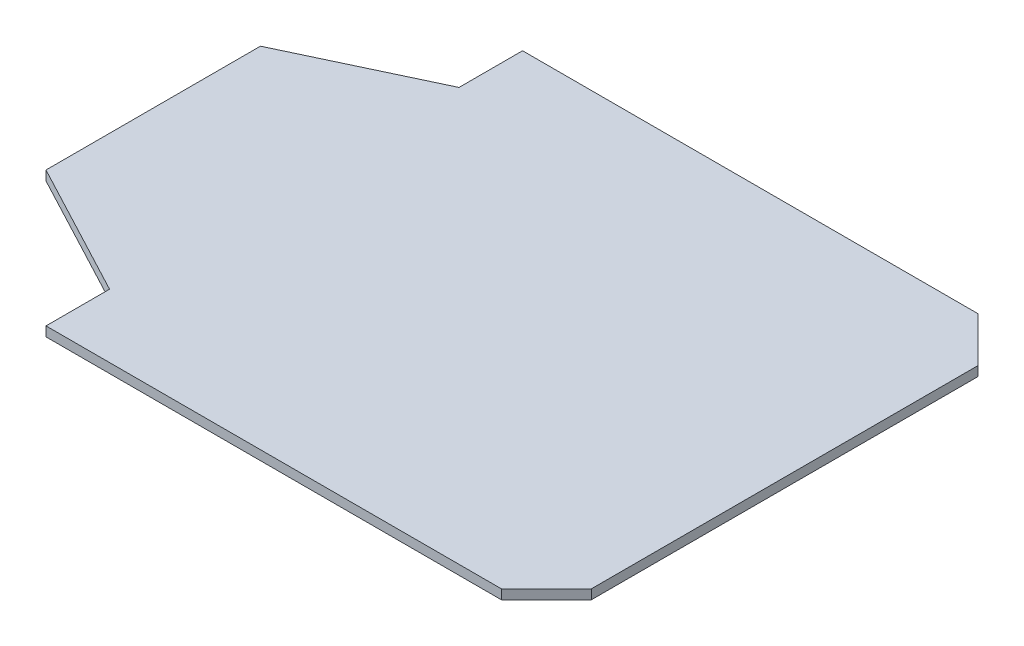
SolidWorks part; units mm, degrees
material "Acrylic (Medium-high impact)"
ref_plane "Front Plane" through (0, 0, 0) normal (0, 0, 1) x (1, 0, 0)
ref_plane "Top Plane" through (0, 0, 0) normal (0, 1, 0) x (1, 0, 0)
ref_plane "Right Plane" through (0, 0, 0) normal (1, 0, 0) x (0, 0, -1)
sketch "Sketch1" plane through (0, 0, 0) normal (0, 1, 0) x (1, 0, 0)
  line L0 (-245.1836, 942.3231) -> (-245.1836, 742.3231)
  line L2 (-145.1836, 692.3231) -> (126.5321, 692.3231)
  line L3 (126.5321, 692.3231) -> (154.8164, 720.6074)
  line L4 (154.8164, 720.6074) -> (154.8164, 964.0388)
  line L6 (126.5321, 992.3231) -> (-145.1836, 992.3231)
  line L8 (126.5321, 992.3231) -> (154.8164, 964.0388)
  line L9 (-145.1836, 692.3231) -> (-245.1836, 692.3231)
  line L10 (-245.1836, 692.3231) -> (-245.1836, 742.3231)
  line L11 (-145.1836, 992.3231) -> (-245.1836, 992.3231)
  line L12 (-245.1836, 992.3231) -> (-245.1836, 942.3231)
  point P2 (154.8164, 842.3231)
  point P9 (-245.1836, 842.3231)
  dimension "D1" = 300
  dimension "D2" = 400
  dimension "D3" = 200
  dimension "D4" = 150
  dimension "D5" = 100
  dimension "D6" = 45
  dimension "D7" = 150
  dimension "D8" = 0
  dimension "D9" = 45
  dimension "D10" = 40
extrude "Boss-Extrude1" add sketch "Sketch1" along normal blind 6 contours L6 L11 L12 L0 L10 L9 L2 L3 L4 L8
sketch "Sketch2" plane through (0, 6, 0) normal (0, 1, 0) x (1, 0, 0)
  line L0 (-245.1836, 912.3231) -> (-160.1836, 952.3231)
  line L1 (-245.1836, 692.3231) -> (-245.1836, 992.3231) construction
  line L2 (-160.1836, 952.3231) -> (-160.1836, 992.3231)
  line L3 (126.5321, 992.3231) -> (-245.1836, 992.3231) construction
  line L4 (-160.1836, 992.3231) -> (-245.1836, 992.3231)
  line L5 (-245.1836, 992.3231) -> (-245.1836, 912.3231)
  line L6 (-245.1836, 777.3231) -> (-160.1836, 732.3231)
  line L7 (-160.1836, 732.3231) -> (-160.1836, 692.3231)
  line L8 (-245.1836, 692.3231) -> (126.5321, 692.3231) construction
  line L9 (-160.1836, 692.3231) -> (-245.1836, 692.3231)
  line L10 (-245.1836, 692.3231) -> (-245.1836, 777.3231)
  dimension "D1" = 40
  dimension "D2" = 45
extrude "Cut-Extrude1" cut sketch "Sketch2" against normal blind 10
